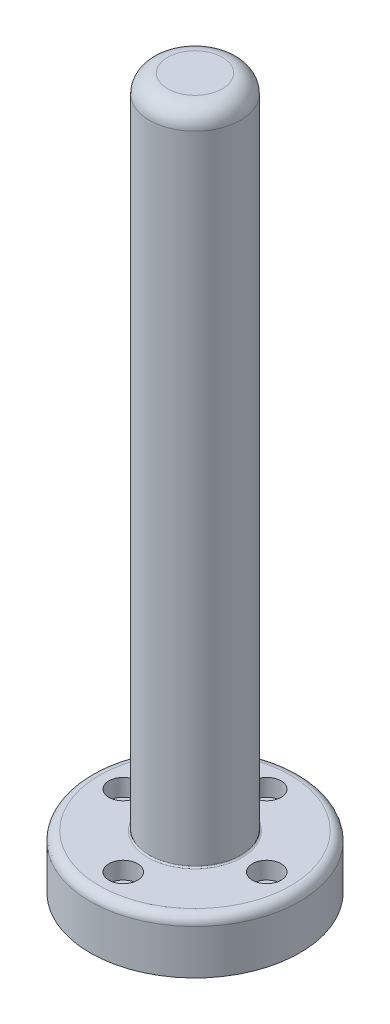
SolidWorks part; units mm, degrees
ref_plane "Front Plane" through (0, 0, 0) normal (0, 0, 1) x (1, 0, 0)
ref_plane "Top Plane" through (0, 0, 0) normal (0, 1, 0) x (1, 0, 0)
ref_plane "Right Plane" through (0, 0, 0) normal (1, 0, 0) x (0, 0, -1)
sketch "Sketch1" plane through (0, 0, 0) normal (0, 1, 0) x (1, 0, 0)
  circle A0 centre (0, 0) radius 31.75
  circle A1 centre (0, 0) radius 36.5125
  dimension "D1" = 63.5
  dimension "D2" = 4.7625
extrude "Boss-Extrude1" add sketch "Sketch1" against normal blind 6.35
extrude "Boss-Extrude2" add sketch "Sketch1<2>" along normal blind 12.35 contours A1
sketch "Sketch1<2>" plane through (0, 0, 0) normal (0, 1, 0) x (1, 0, 0) same geometry as "Sketch1"
sketch "Sketch2" plane through (0, 12.35, 0) normal (0, 1, 0) x (1, 0, 0)
  line L0 (0, 36.5125) -> (0, 0) construction
  circle A0 centre (0, 0) radius 36.5125 construction
  circle A1 centre (0, 25) radius 3.3
  circle A2 centre (25, 0) radius 3.3
  circle A3 centre (0, -25) radius 3.3
  circle A4 centre (-25, 0) radius 3.3
  point P16 (0, 0)
  dimension "D2" = 6.6
  dimension "D1" = 25
  dimension "D3" = 4
extrude "Cut-Extrude1" cut sketch "Sketch2" against normal through all both and the other way through all
sketch "Sketch3" plane through (0, 12.35, 0) normal (0, 1, 0) x (1, 0, 0)
  circle A0 centre (0, 0) radius 15.875
  dimension "D1" = 31.75
extrude "Boss-Extrude3" add sketch "Sketch3" along normal blind 228.6
sketch "Sketch4" plane through (0, 12.35, 0) normal (0, 1, 0) x (1, 0, 0)
  circle A0 centre (-25, 0) radius 5
  circle A1 centre (0, 25) radius 5
  circle A2 centre (25, 0) radius 5
  circle A3 centre (0, -25) radius 5
  point P12 (0, 0)
  dimension "D1" = 10
  dimension "D2" = 4
extrude "Cut-Extrude2" cut sketch "Sketch4" against normal blind 6 and the other way through all
fillet "Fillet2" radius 0.508 1 edges at (0, 12.35, 15.875)
fillet "Fillet3" radius 3.175 1 edges at (0, 12.35, 36.5125)
sketch "Sketch5" plane through (0, 240.95, 0) normal (0, 1, 0) x (1, 0, 0)
  circle A0 centre (0, 0) radius 9.525
  circle A1 centre (0, 0) radius 15.875 construction
  dimension "D1" = 6.35
extrude "Cut-Extrude3" cut sketch "Sketch5" against normal blind 222.25
fillet "Fillet4" radius 6.35 1 edges at (0, 18.7, 9.525)
sketch "Sketch6" plane through (0, 240.95, 0) normal (0, 1, 0) x (1, 0, 0)
  circle A0 centre (0, 0) radius 15.875
extrude "Boss-Extrude4" add sketch "Sketch6" against normal blind 6.35
fillet "Fillet5" radius 6.35 2 edges at (0, 240.95, 15.875) (0, 234.6, 9.525)
